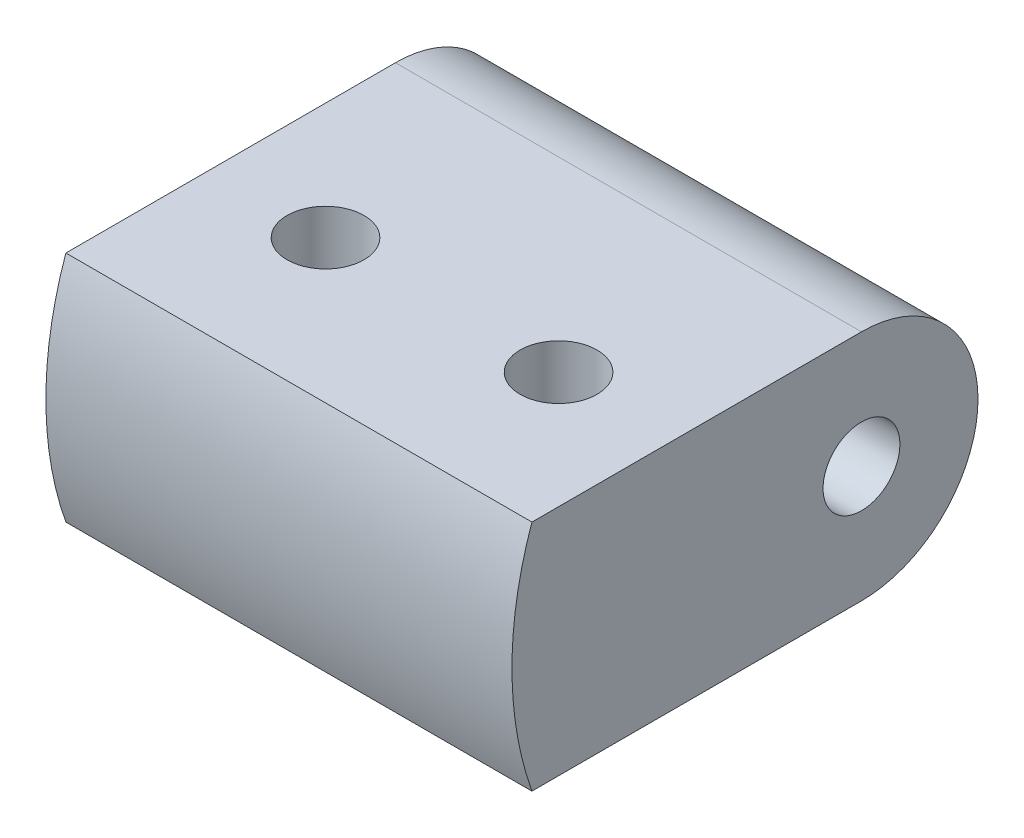
SolidWorks part; units mm, degrees
ref_plane "Front Plane" through (0, 0, 0) normal (0, 0, 1) x (1, 0, 0)
ref_plane "Top Plane" through (0, 0, 0) normal (0, 1, 0) x (1, 0, 0)
ref_plane "Right Plane" through (0, 0, 0) normal (1, 0, 0) x (0, 0, -1)
sketch "Sketch1" plane through (0, 0, 0) normal (0, 1, 0) x (1, 0, 0)
  line L1 (-10, -10) -> (10, -10)
  line L2 (-10, -10) -> (-10, 10)
  line L3 (-10, 10) -> (10, 10)
  line L4 (10, -10) -> (10, 10)
  line L5 (-10, -10) -> (10, 10) construction
  line L6 (-10, 10) -> (10, -10) construction
  point P0 (0, 0)
  dimension "D1" = 20
  dimension "D2" = 20
extrude "Boss-Extrude1" add sketch "Sketch1" along normal blind 10
fillet "Fillet1" radius 5 2 edges at (0, 0, -10) (0, 10, -10)
hole_wizard "M4x0.7 Tapped Hole1" positions "Sketch2" profile "Sketch4" tap size "M4x0.7" standard "ANSI Metric" end condition up to next
sketch "Sketch2" plane through (10, 0, 0) normal (1, 0, 0) x (0, 0, -1)
  line L0 (5, 10) -> (5, 0)
  point P6 (5, 5)
sketch "Sketch4" plane through (10, 5, -5) normal (0, 1, 0) x (0, 0, -1)
  line L0 (0, 0) -> (0, 20)
  line L1 (0, 20) -> (1.65, 20)
  line L2 (1.65, 20) -> (1.65, 0)
  line L5 (1.65, 0) -> (0, 0)
  line L11 (0, -6.35) -> (0, 107.95) construction
  dimension "Thru Tap Drill Dia." = 3.3
  dimension "Thru Tap Drill Depth" = 20
cosmetic thread "Hole Thread1" parameters "D2"=4
hole_wizard "M4x0.7 Tapped Hole2" positions "Sketch7" profile "Sketch8" tap size "M4x0.7" standard "ANSI Metric" end condition up to next
sketch "Sketch7" plane through (0, 10, 0) normal (0, 1, 0) x (1, 0, 0)
  line L0 (-5, -3) -> (5, -3)
  point P0 (-5, -3)
  point P1 (5, -3)
  point P4 (0, -3)
  dimension "D1" = 10
  dimension "D2" = 7
sketch "Sketch8" plane through (-5, 10, 3) normal (1, 0, 0) x (0, 0, 1)
  line L0 (0, 0) -> (0, 10)
  line L1 (0, 10) -> (1.65, 10)
  line L2 (1.65, 10) -> (1.65, 0)
  line L5 (1.65, 0) -> (0, 0)
  line L11 (0, -6.35) -> (0, 107.95) construction
  dimension "Thru Tap Drill Dia." = 3.3
  dimension "Thru Tap Drill Depth" = 10
cosmetic thread "Hole Thread4" parameters "D2"=4
cosmetic thread "Hole Thread5" parameters "D2"=4
sketch "Sketch9" plane through (10, 0, 0) normal (1, 0, 0) x (0, 0, -1)
  line L1 (20, 0) -> (-10, 0)
  line L2 (20, 0) -> (20, 10)
  line L3 (20, 10) -> (-10, 10)
  line L4 (-10, 0) -> (-10, 10)
  line L5 (20, 0) -> (-10, 10) construction
  line L6 (20, 10) -> (-10, 0) construction
  circle A0 centre (5, 5) radius 15
  line M7 (-10, 0) -> (5, 0)
  line M11 (-10, 10) -> (-10, 0)
extrude "Cut-Extrude1" cut sketch "Sketch9" against normal through all contours A0 L3 M11 | A0 L4 M7 region at (10, 1.2427, 9.744) region at (10, 8.7573, 9.744)
